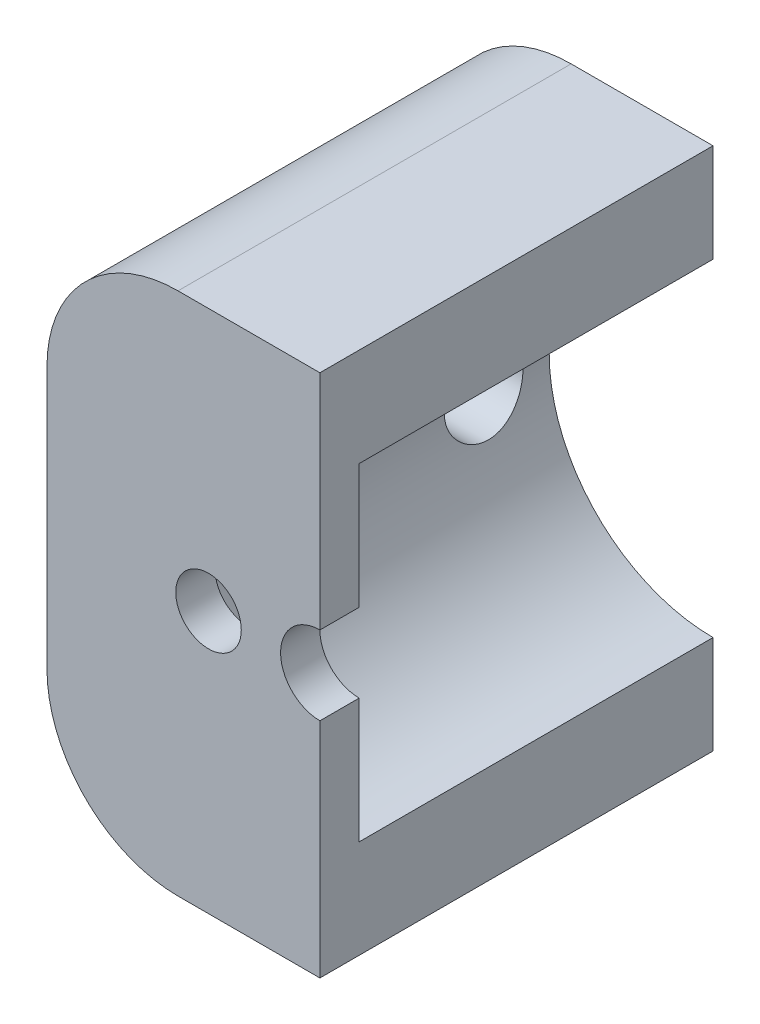
SolidWorks part; units mm, degrees
ref_plane "Front Plane" through (0, 0, 0) normal (0, 0, 1) x (1, 0, 0)
ref_plane "Top Plane" through (0, 0, 0) normal (0, 1, 0) x (1, 0, 0)
ref_plane "Right Plane" through (0, 0, 0) normal (1, 0, 0) x (0, 0, -1)
sketch "Sketch1" plane through (0, 0, 0) normal (0, 0, 1) x (1, 0, 0)
  line L0 (0, 20) -> (0, -20) construction
  line L1 (-20.8276, 20) -> (0, 20)
  line L2 (-20.8276, 20) -> (-20.8276, -20)
  line L3 (-20.8276, -20) -> (0, -20)
  line L5 (-20.8276, 20) -> (0, 0) construction
  line L6 (-20.8276, -20) -> (0, 0) construction
  line L7 (0, 20) -> (0, 12.5)
  line L8 (0, -20) -> (0, -12.5)
  arc A0 (0, 12.5) -> (0, -12.5) centre (0, 0) ccw
  point P6 (-20.8276, 0)
  dimension "D1" = 25
  dimension "D3" = 40
extrude "Boss-Extrude1" add sketch "Sketch1" along normal blind 30
sketch "Sketch2" plane through (0, 0, 30) normal (0, 0, 1) x (1, 0, 0)
  line L0 (0, 12.5) -> (0, 3)
  line L1 (0, -3) -> (0, -12.5)
  arc A0 (0, 12.5) -> (0, -12.5) centre (0, 0) ccw construction
  arc A1 (0, 12.5) -> (0, -12.5) centre (0, 0) ccw
  arc A2 (0, 3) -> (0, -3) centre (0, 0) ccw
  circle A3 centre (-8.5, 0) radius 2.5
  dimension "D1" = 6
  dimension "D2" = 5
extrude "Boss-Extrude2" add sketch "Sketch2" against normal blind 3
sketch "Sketch3" plane through (0, 0, 0) normal (1, 0, 0) x (0, 0, -1)
  circle A0 centre (-5, 0) radius 2
  circle A1 centre (-5, 0) radius 3
  circle A2 centre (-20, 0) radius 2
  circle A3 centre (-20, 0) radius 3
  dimension "D2" = 4
  dimension "D3" = 6
  dimension "D1" = 15
  dimension "D4" = 5
extrude "Cut-Extrude1" cut sketch "Sketch3" against normal through all contours A2 | A0 region at (0, 0, 5) region at (0, 0, 20)
extrude "Cut-Extrude7" cut sketch "Sketch3<4>" against normal blind 17
sketch "Sketch3<4>" plane through (0, 0, 0) normal (1, 0, 0) x (0, 0, -1) same geometry as "Sketch3"
fillet "Fillet1" radius 10 2 edges at (-20.8276, -20, 15) (-20.8276, 20, 15)
